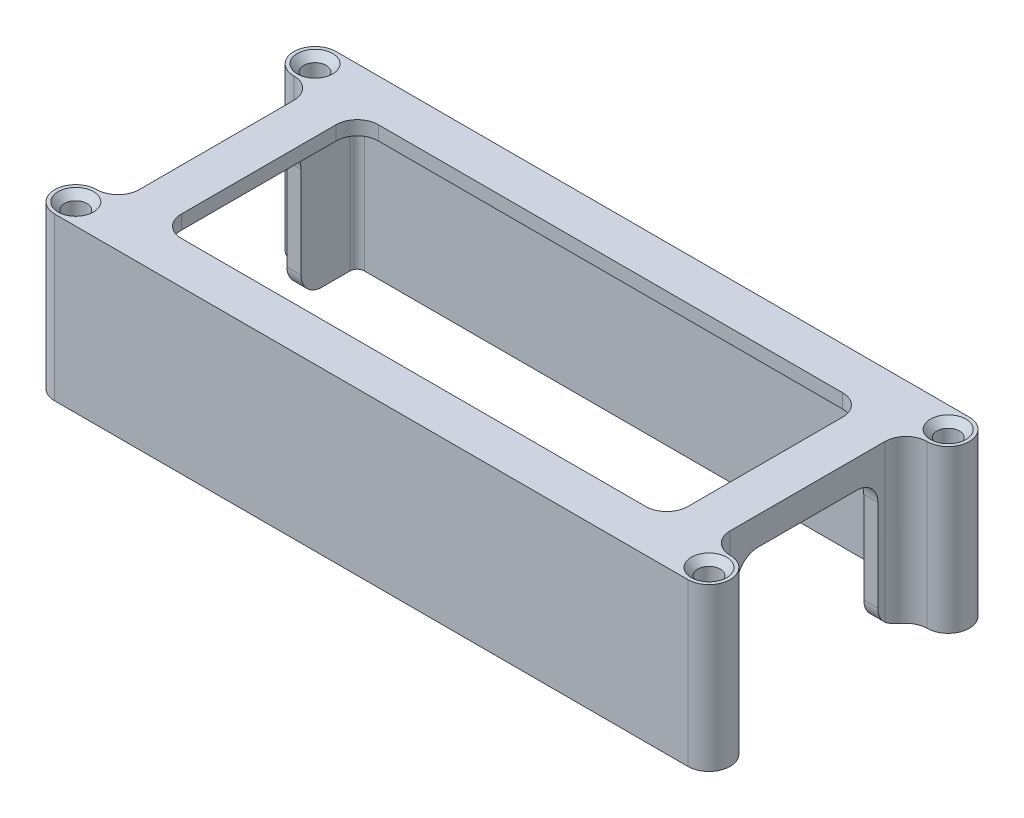
SolidWorks part; units mm, degrees
ref_plane "Front Plane" through (0, 0, 0) normal (0, 0, 1) x (1, 0, 0)
ref_plane "Top Plane" through (0, 0, 0) normal (0, 1, 0) x (1, 0, 0)
ref_plane "Right Plane" through (0, 0, 0) normal (1, 0, 0) x (0, 0, -1)
sketch "Sketch1" plane through (0, 0, 0) normal (0, 1, 0) x (1, 0, 0)
  line L0 (63.5, 28.575) -> (66.675, 31.75) construction
  line L1 (-63.5, -28.575) -> (63.5, -28.575)
  line L2 (-63.5, -28.575) -> (-63.5, 28.575)
  line L3 (-63.5, 28.575) -> (63.5, 28.575)
  line L4 (63.5, -28.575) -> (63.5, 28.575)
  line L5 (-63.5, -28.575) -> (63.5, 28.575) construction
  line L6 (-63.5, 28.575) -> (63.5, -28.575) construction
  line L7 (-66.675, -31.75) -> (66.675, -31.75)
  line L8 (-66.675, -31.75) -> (-66.675, 31.75)
  line L9 (-66.675, 31.75) -> (66.675, 31.75)
  line L10 (66.675, -31.75) -> (66.675, 31.75)
  line L11 (-66.675, -31.75) -> (66.675, 31.75) construction
  line L12 (-66.675, 31.75) -> (66.675, -31.75) construction
  line L13 (63.5, -28.575) -> (66.675, -31.75) construction
  point P0 (0, 0)
  point P6 (0, 0)
  dimension "D1" = 57.15
  dimension "D2" = 127
  dimension "D3" = 3.175
extrude "Boss-Extrude1" add sketch "Sketch1" along normal blind 33.3375
sketch "Sketch2" plane through (-66.675, 0, 0) normal (-1, 0, 0) x (0, 0, 1)
  line L0 (-31.75, 0) -> (31.75, 0) construction
  line L1 (-15.875, -30.1625) -> (15.875, -30.1625)
  line L2 (-15.875, -30.1625) -> (-15.875, 30.1625)
  line L3 (-15.875, 30.1625) -> (15.875, 30.1625)
  line L4 (15.875, -30.1625) -> (15.875, 30.1625)
  line L5 (-15.875, -30.1625) -> (15.875, 30.1625) construction
  line L6 (-15.875, 30.1625) -> (15.875, -30.1625) construction
  point P0 (0, 0)
  dimension "D1" = 31.75
  dimension "D2" = 30.1625
extrude "Cut-Extrude1" cut sketch "Sketch2" against normal through all
sketch "Sketch3" plane through (0, 33.3375, 0) normal (0, 1, 0) x (1, 0, 0)
  line L0 (-66.675, 31.75) -> (-57.15, 22.225) construction
  line L1 (57.15, -22.225) -> (-57.15, -22.225)
  line L2 (57.15, -22.225) -> (57.15, 22.225)
  line L3 (57.15, 22.225) -> (-57.15, 22.225)
  line L4 (66.675, -31.75) -> (66.675, 31.75)
  line L5 (66.675, 31.75) -> (-66.675, 31.75)
  line L6 (-66.675, 31.75) -> (-66.675, -31.75)
  line L7 (-66.675, -31.75) -> (66.675, -31.75)
  line L8 (66.675, -31.75) -> (66.675, 31.75)
  line L9 (66.675, 31.75) -> (-66.675, 31.75)
  line L10 (-66.675, 31.75) -> (-66.675, -31.75)
  line L11 (-66.675, -31.75) -> (66.675, -31.75)
  line L12 (-57.15, -22.225) -> (-57.15, 22.225)
  line L13 (57.15, -22.225) -> (-57.15, 22.225) construction
  line L14 (57.15, 22.225) -> (-57.15, -22.225) construction
  line L15 (-66.675, -31.75) -> (-57.15, -22.225) construction
  line L16 (63.5, 28.575) -> (-63.5, 28.575) construction
  point P2 (0, 0)
  dimension "D2" = 6.35
  dimension "D1" = 0
extrude "Boss-Extrude2" add sketch "Sketch3" along normal blind 3.175
sketch "Sketch4" plane through (0, 36.5125, 0) normal (0, 1, 0) x (1, 0, 0)
  line L0 (66.675, -31.75) -> (66.675, 31.75) construction
  line L1 (71.4375, 31.75) -> (66.675, 31.75)
  line L2 (66.675, 31.75) -> (66.675, 17.4625)
  circle A0 centre (71.4375, 26.9875) radius 1.27 construction
  arc A1 (71.4375, 31.75) -> (71.4375, 22.225) centre (71.4375, 26.9875) cw
  arc A2 (66.675, 17.4625) -> (71.4375, 22.225) centre (71.4375, 17.4625) cw
  dimension "D1" = 4.7625
  dimension "D2" = 2.54
extrude "Boss-Extrude3" add sketch "Sketch4" against normal up to surface (36.5125 mm away) up to face at (0, 0, -23.0187)
ref_axis "Axis1" through (71.4375, 0, -26.9875) along (0, 1, 0)
ref_plane "Plane1" through (71.4375, 0, 0) normal (1, 0, 0) x (0, 1, 0)
sketch "Sketch5" plane through (71.4375, 0, 0) normal (1, 0, 0) x (0, 1, 0)
  line L0 (0, -29.5275) -> (34.925, -29.5275)
  line L1 (34.925, -29.5275) -> (36.5125, -30.9822)
  line L2 (36.5125, -31.75) -> (36.5125, -22.225) construction
  line L3 (36.5125, -30.9822) -> (36.5125, -26.9875)
  line L4 (36.5125, -26.9875) -> (0, -26.9875) construction
  line L5 (0, -26.9875) -> (36.5125, -26.9875) construction
  line L6 (0, -26.9875) -> (0, -29.5275)
  line L7 (0, -22.225) -> (0, -31.75) construction
  line L8 (36.5125, -26.9875) -> (0, -26.9875)
  dimension "D1" = 5.08
  dimension "D2" = 42.5
  dimension "D3" = 1.5875
revolve "Cut-Revolve1" cut sketch "Sketch5" angle 360 about L8
mirror "Mirror1" about plane through (0, 0, 0) normal (0, 0, 1) of "Cut-Revolve1", "Boss-Extrude3"
mirror "Mirror2" about plane through (0, 0, 0) normal (1, 0, 0) of "Cut-Revolve1", "Boss-Extrude3", "Mirror1"
fillet "Fillet1" radius 1.5875 8 edges at (63.5, 16.6687, -28.575) (-63.5, 16.6687, 28.575) (-63.5, 16.6687, -28.575) (-63.5, 33.3375, 0) (0, 33.3375, -28.575) (63.5, 16.6687, 28.575) (63.5, 33.3375, 0) (0, 33.3375, 28.575)
fillet "Fillet2" radius 4.7625 12 edges at (65.0875, 0, 15.875) (65.0875, 0, -15.875) (-65.0875, 0, 15.875) (-65.0875, 0, -15.875) (-65.0875, 30.1625, -15.875) (-65.0875, 30.1625, 15.875) (65.0875, 30.1625, 15.875) (65.0875, 30.1625, -15.875) (-57.15, 34.925, 22.225) (-57.15, 34.925, -22.225) (57.15, 34.925, 22.225) (57.15, 34.925, -22.225)
